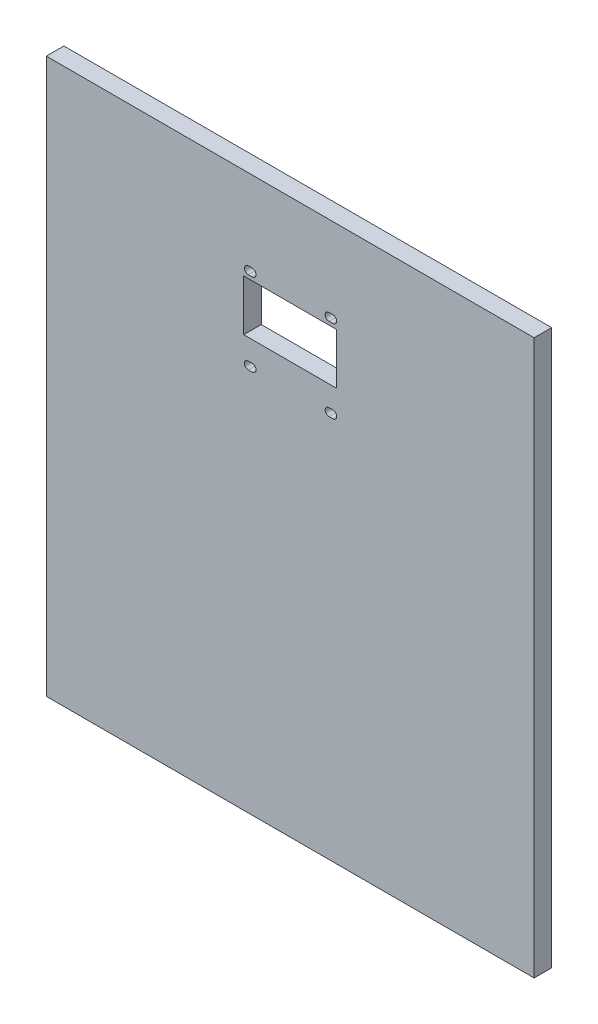
SolidWorks part; units mm, degrees
ref_plane "Front Plane" through (0, 0, 0) normal (0, 0, 1) x (1, 0, 0)
ref_plane "Top Plane" through (0, 0, 0) normal (0, 1, 0) x (1, 0, 0)
ref_plane "Right Plane" through (0, 0, 0) normal (1, 0, 0) x (0, 0, -1)
sketch "Sketch1" plane through (0, 0, 0) normal (0, 0, 1) x (1, 0, 0)
  line L0 (58.657, 135.0332) -> (57.557, 135.0332) construction
  line L1 (0, 0) -> (139, 0)
  line L2 (0, 0) -> (0, 158)
  line L3 (0, 158) -> (139, 158)
  line L4 (139, 0) -> (139, 158)
  line L9 (82.75, 131.8832) -> (56.25, 131.8832)
  line L10 (82.75, 131.8832) -> (82.75, 117.3832)
  line L11 (82.75, 117.3832) -> (56.25, 117.3832)
  line L12 (56.25, 131.8832) -> (56.25, 117.3832)
  line L13 (81.657, 135.0332) -> (80.557, 135.0332) construction
  line L14 (80.557, 132.8332) -> (81.657, 132.8332) construction
  line L15 (58.657, 135.0332) -> (57.557, 135.0332)
  line L16 (81.657, 135.0332) -> (80.557, 135.0332)
  line L17 (80.557, 132.8332) -> (81.657, 132.8332)
  line L18 (57.557, 132.8332) -> (58.657, 132.8332) construction
  line L19 (57.557, 132.8332) -> (58.657, 132.8332)
  line L20 (57.557, 109.3332) -> (58.657, 109.3332) construction
  line L21 (58.657, 111.5332) -> (57.557, 111.5332) construction
  line L22 (57.557, 109.3332) -> (58.657, 109.3332)
  line L23 (58.657, 111.5332) -> (57.557, 111.5332)
  line L24 (80.557, 109.3332) -> (81.657, 109.3332) construction
  line L25 (81.657, 111.5332) -> (80.557, 111.5332) construction
  line L26 (80.557, 109.3332) -> (81.657, 109.3332)
  line L27 (81.657, 111.5332) -> (80.557, 111.5332)
  arc A4 (80.557, 135.0332) -> (80.557, 132.8332) centre (80.557, 133.9332) ccw construction
  arc A5 (81.657, 132.8332) -> (81.657, 135.0332) centre (81.657, 133.9332) ccw construction
  arc A6 (80.557, 135.0332) -> (80.557, 132.8332) centre (80.557, 133.9332) ccw
  arc A7 (81.657, 132.8332) -> (81.657, 135.0332) centre (81.657, 133.9332) ccw
  arc A8 (57.557, 135.0332) -> (57.557, 132.8332) centre (57.557, 133.9332) ccw construction
  arc A9 (58.657, 132.8332) -> (58.657, 135.0332) centre (58.657, 133.9332) ccw construction
  arc A10 (57.557, 135.0332) -> (57.557, 132.8332) centre (57.557, 133.9332) ccw
  arc A11 (58.657, 132.8332) -> (58.657, 135.0332) centre (58.657, 133.9332) ccw
  arc A12 (57.557, 111.5332) -> (57.557, 109.3332) centre (57.557, 110.4332) ccw construction
  arc A13 (58.657, 109.3332) -> (58.657, 111.5332) centre (58.657, 110.4332) ccw construction
  arc A14 (57.557, 111.5332) -> (57.557, 109.3332) centre (57.557, 110.4332) ccw
  arc A15 (58.657, 109.3332) -> (58.657, 111.5332) centre (58.657, 110.4332) ccw
  arc A16 (81.657, 109.3332) -> (81.657, 111.5332) centre (81.657, 110.4332) ccw construction
  arc A17 (80.557, 111.5332) -> (80.557, 109.3332) centre (80.557, 110.4332) ccw construction
  arc A18 (81.657, 109.3332) -> (81.657, 111.5332) centre (81.657, 110.4332) ccw
  arc A19 (80.557, 111.5332) -> (80.557, 109.3332) centre (80.557, 110.4332) ccw
  point P5 (69.5, 131.8832)
  point P6 (69.5, 158)
  point P17 (0, 0)
  dimension "D1" = 139
  dimension "D2" = 158
  dimension "D4" = 26.5
  dimension "D5" = 14.5
extrude "Boss-Extrude1" add sketch "Sketch1" along normal blind 5
